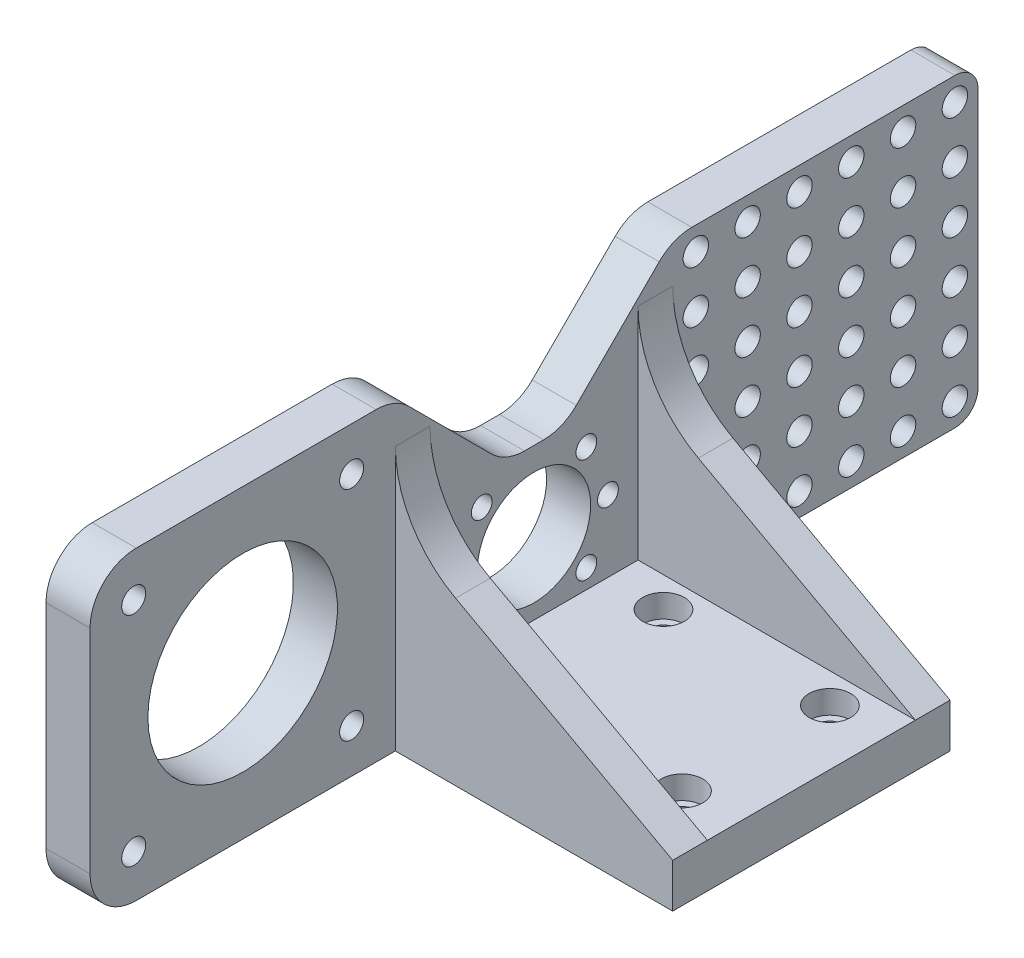
SolidWorks part; units mm, degrees
ref_plane "Front Plane" through (0, 0, 0) normal (0, 0, 1) x (1, 0, 0)
ref_plane "Top Plane" through (0, 0, 0) normal (0, 1, 0) x (1, 0, 0)
ref_plane "Right Plane" through (0, 0, 0) normal (1, 0, 0) x (0, 0, -1)
sketch "Sketch1" plane through (0, 0, 0) normal (0, 1, 0) x (1, 0, 0)
  line L0 (30, 60) -> (30, 0) construction
  line L1 (0, 0) -> (60, 0)
  line L2 (0, 0) -> (0, 60)
  line L3 (0, 60) -> (60, 60)
  line L4 (60, 0) -> (60, 60)
  line L5 (12, 46) -> (48, 46) construction
  line L6 (12, 46) -> (12, 14) construction
  line L7 (12, 14) -> (48, 14) construction
  line L8 (48, 46) -> (48, 14) construction
  line L9 (0, 30) -> (60, 30) construction
  circle A0 centre (12, 14) radius 2.95
  circle A1 centre (12, 46) radius 2.95
  circle A2 centre (48, 46) radius 2.95
  circle A3 centre (48, 14) radius 2.95
  dimension "D3" = 5.9
  dimension "D1" = 36
  dimension "D2" = 32
  dimension "D4" = 60
  dimension "D5" = 60
extrude "Boss-Extrude1" add sketch "Sketch1" along normal blind 9.525
sketch "Sketch2" plane through (0, 9.525, 0) normal (0, 1, 0) x (1, 0, 0)
  circle A0 centre (12, 14) radius 4.5
  circle A1 centre (12, 46) radius 4.5
  circle A2 centre (48, 46) radius 4.5
  circle A3 centre (48, 14) radius 4.5
  dimension "D1" = 9
extrude "Cut-Extrude1" cut sketch "Sketch2" against normal blind 5
sketch "Sketch3" plane through (0, 0, 0) normal (-1, 0, 0) x (0, 0, 1)
  line L0 (-60, 9.525) -> (0, 9.525) construction
  line L1 (-60, 0) -> (0, 0)
  line L2 (-60, 0) -> (-60, 42.25)
  line L3 (-60, 42.25) -> (0, 42.25)
  line L4 (0, 0) -> (0, 42.25)
  line L6 (0, 9.525) -> (0, 0) construction
  line L7 (-30, 44.025) -> (-30, 0) construction
  line L8 (-30, 25) -> (0, 25) construction
  line L9 (-30, 25) -> (-18.6863, 36.3137) construction
  circle A0 centre (-30, 25) radius 12.25
  circle A1 centre (-30, 25) radius 16 construction
  circle A2 centre (-18.6863, 36.3137) radius 2.25
  circle A3 centre (-14, 25) radius 2.25
  circle A4 centre (-18.6863, 13.6863) radius 2.25
  circle A5 centre (-41.3137, 13.6863) radius 2.25
  circle A6 centre (-46, 25) radius 2.25
  circle A7 centre (-41.3137, 36.3137) radius 2.25
  point P14 (-30, 42.25)
  dimension "D1" = 24.5
  dimension "D2" = 15.475
  dimension "D3" = 5
  dimension "D4" = 32
  dimension "D6" = 4.5
  dimension "D5" = 45
  dimension "D7" = 3
extrude "Boss-Extrude2" add sketch "Sketch3" along normal blind 9.525
sketch "Sketch4" plane through (-9.525, 0, 0) normal (-1, 0, 0) x (0, 0, 1)
  line L0 (33.02, 72.7999) -> (33.02, 6.7599) construction
  line L1 (0, 0) -> (66.04, 0)
  line L2 (0, 0) -> (0, 66.04)
  line L3 (0, 66.04) -> (66.04, 66.04)
  line L4 (66.04, 0) -> (66.04, 66.04)
  line L5 (9.45, 56.59) -> (56.59, 56.59) construction
  line L6 (9.45, 56.59) -> (9.45, 9.45) construction
  line L7 (9.45, 9.45) -> (56.59, 9.45) construction
  line L8 (56.59, 56.59) -> (56.59, 9.45) construction
  line L9 (46.2537, 33.02) -> (-19.7863, 33.02) construction
  line L11 (0, 0) -> (0, 42.25) construction
  line L14 (-60, 0) -> (0, 0) construction
  line L15 (-30, 98.1688) -> (-30, 122.9789) construction
  line L16 (-60, 66.04) -> (-126.04, 66.04)
  line L17 (-126.04, 0) -> (-126.04, 66.04)
  line L18 (-60, 0) -> (-126.04, 0)
  line L19 (-60, 0) -> (-60, 66.04)
  circle A0 centre (56.59, 56.59) radius 2.6
  circle A1 centre (9.45, 56.59) radius 2.6
  circle A2 centre (9.45, 9.45) radius 2.6
  circle A3 centre (56.59, 9.45) radius 2.6
  circle A4 centre (33.02, 33.02) radius 20.5
  circle A6 centre (-30, 25) radius 12.25 construction
  circle A7 centre (-121.04, 61.04) radius 2.75
  circle A8 centre (-109.832, 61.04) radius 2.75
  circle A9 centre (-98.624, 61.04) radius 2.75
  circle A10 centre (-87.416, 61.04) radius 2.75
  circle A11 centre (-76.208, 61.04) radius 2.75
  circle A12 centre (-65, 61.04) radius 2.75
  circle A13 centre (-109.832, 49.832) radius 2.75
  circle A14 centre (-98.624, 49.832) radius 2.75
  circle A15 centre (-87.416, 49.832) radius 2.75
  circle A16 centre (-76.208, 49.832) radius 2.75
  circle A17 centre (-65, 49.832) radius 2.75
  circle A18 centre (-109.832, 38.624) radius 2.75
  circle A19 centre (-98.624, 38.624) radius 2.75
  circle A20 centre (-87.416, 38.624) radius 2.75
  circle A21 centre (-76.208, 38.624) radius 2.75
  circle A22 centre (-65, 38.624) radius 2.75
  circle A23 centre (-109.832, 27.416) radius 2.75
  circle A24 centre (-98.624, 27.416) radius 2.75
  circle A25 centre (-87.416, 27.416) radius 2.75
  circle A26 centre (-76.208, 27.416) radius 2.75
  circle A27 centre (-65, 27.416) radius 2.75
  circle A28 centre (-109.832, 16.208) radius 2.75
  circle A29 centre (-98.624, 16.208) radius 2.75
  circle A30 centre (-87.416, 16.208) radius 2.75
  circle A31 centre (-76.208, 16.208) radius 2.75
  circle A32 centre (-65, 16.208) radius 2.75
  circle A33 centre (-109.832, 5) radius 2.75
  circle A34 centre (-98.624, 5) radius 2.75
  circle A35 centre (-87.416, 5) radius 2.75
  circle A36 centre (-76.208, 5) radius 2.75
  circle A37 centre (-65, 5) radius 2.75
  circle A38 centre (-121.04, 49.832) radius 2.75
  circle A39 centre (-121.04, 38.624) radius 2.75
  circle A40 centre (-121.04, 27.416) radius 2.75
  circle A41 centre (-121.04, 16.208) radius 2.75
  circle A42 centre (-121.04, 5) radius 2.75
  point P17 (66.04, 33.02)
  point P18 (33.02, 66.04)
  point P28 (-30, 25)
  dimension "D3" = 5.2
  dimension "D5" = 41
  dimension "D6" = 5.5
  dimension "D1" = 66.04
  dimension "D2" = 66.04
  dimension "D4" = 47.14
  dimension "D7" = 5
  dimension "D8" = 5
  dimension "D11" = 5
  dimension "D12" = 5
  dimension "D9" = 6
  dimension "D10" = 6
extrude "Boss-Extrude3" add sketch "Sketch4" against normal blind 9.525
sketch "Sketch5" plane through (0, 0, 0) normal (0, 0, 1) x (1, 0, 0)
  line L0 (60, 9.525) -> (0, 42.25)
  line L1 (0, 9.525) -> (60, 9.525) construction
  line L2 (0, 0) -> (0, 66.04) construction
  line L3 (0, 42.25) -> (0, 9.525)
  line L4 (0, 9.525) -> (60, 9.525)
  dimension "D1" = 60
  dimension "D2" = 32.725
extrude "Boss-Extrude4" add sketch "Sketch5" against normal blind 7.5
ref_plane "Plane1" through (0, 0, -30) normal (0, 0, 1) x (1, 0, 0)
mirror "Mirror1" about plane through (0, 0, -30) normal (0, 0, 1) of "Boss-Extrude4"
chamfer "Chamfer1" distance 23.79 angle 45 2 edges at (-4.7625, 42.25, -60) (-4.7625, 42.25, 0)
fillet "Fillet1" radius 10 6 edges at (-4.7625, 42.25, -36.21) (-4.7625, 42.25, -23.79) (-4.7625, 0, 66.04) (-4.7625, 66.04, 66.04) (-4.7625, 66.04, -60) (-4.7625, 66.04, 0)
fillet "Fillet2" radius 5 2 edges at (-4.7625, 0, -126.04) (-4.7625, 66.04, -126.04)
fillet "Fillet3" radius 25 2 edges at (0, 42.25, -56.25) (0, 42.25, -3.75)
